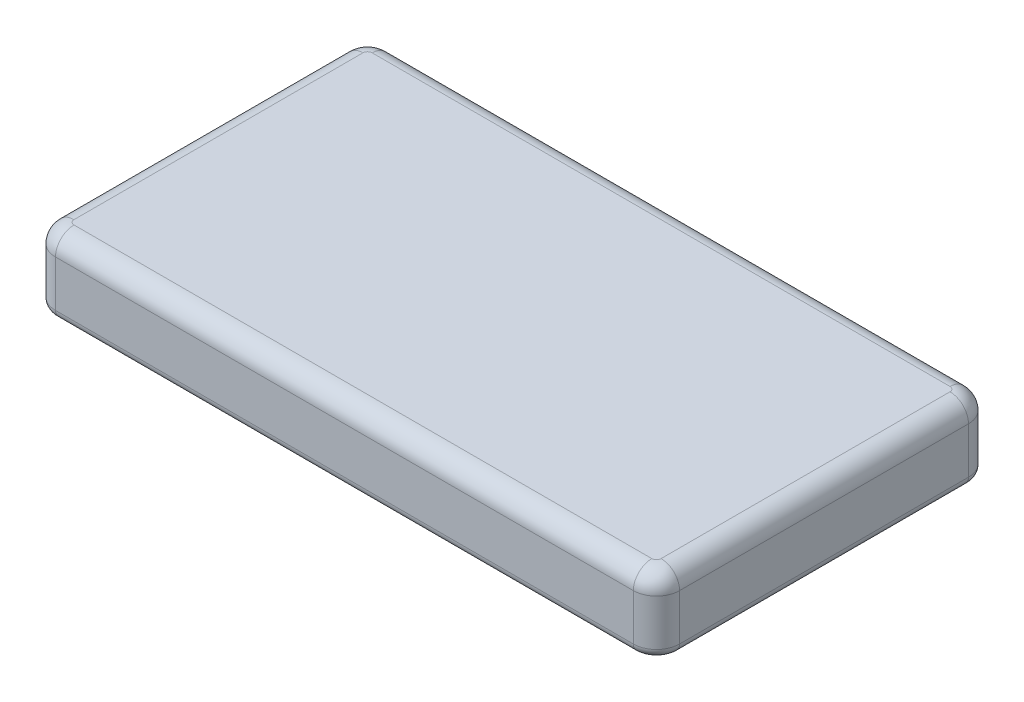
SolidWorks part; units mm, degrees
ref_plane "Front Plane" through (0, 0, 0) normal (0, 0, 1) x (1, 0, 0)
ref_plane "Top Plane" through (0, 0, 0) normal (0, 1, 0) x (1, 0, 0)
ref_plane "Right Plane" through (0, 0, 0) normal (1, 0, 0) x (0, 0, -1)
sketch "Sketch1" plane through (0, 0, 0) normal (0, 1, 0) x (1, 0, 0)
  line L1 (-135, 72.5) -> (135, 72.5)
  line L2 (-135, 72.5) -> (-135, -72.5)
  line L3 (-135, -72.5) -> (135, -72.5)
  line L4 (135, 72.5) -> (135, -72.5)
  line L5 (-135, 72.5) -> (135, -72.5) construction
  line L6 (-135, -72.5) -> (135, 72.5) construction
  point P0 (0, 0)
  dimension "D1" = 270
  dimension "D2" = 145
extrude "Boss-Extrude1" add sketch "Sketch1" along normal blind 32
fillet "Fillet1" radius 8 4 edges at (135, 32, 0) (0, 32, -72.5) (-135, 32, 0) (0, 32, 72.5)
fillet "Fillet2" radius 10 8 edges at (132.6569, 29.6569, 70.1569) (132.6569, 29.6569, -70.1569) (-132.6569, 29.6569, 70.1569) (-132.6569, 29.6569, -70.1569) (-135, 12, -72.5) (-135, 12, 72.5) (135, 12, -72.5) (135, 12, 72.5)
fillet "Fillet3" radius 4 8 edges at (132.0711, 0, -69.5711) (135, 0, 0) (132.0711, 0, 69.5711) (0, 0, 72.5) (-132.0711, 0, 69.5711) (-135, 0, 0) (-132.0711, 0, -69.5711) (0, 0, -72.5)
sketch "Sketch2" plane through (-135, 0, 0) normal (-1, 0, 0) x (0, 0, 1)
  line L0 (-62.5, 14) -> (62.5, 14) construction
  line L1 (-62.5, 24) -> (-62.5, 4) construction
  line L2 (62.5, 4) -> (62.5, 24) construction
  line L4 (-11.5769, 18.0401) -> (11.5769, 18.0401)
  line L5 (-11.5769, 18.0401) -> (-11.5769, 9.9599)
  line L6 (-11.5769, 9.9599) -> (11.5769, 9.9599)
  line L7 (11.5769, 18.0401) -> (11.5769, 9.9599)
  line L8 (-11.5769, 18.0401) -> (11.5769, 9.9599) construction
  line L9 (-11.5769, 9.9599) -> (11.5769, 18.0401) construction
  circle A0 centre (-45.2002, 14) radius 3.522
  circle A1 centre (48.2203, 14) radius 4.7074
  point P8 (0, 14)
extrude "Cut-Extrude1" cut sketch "Sketch2" against normal blind 33
